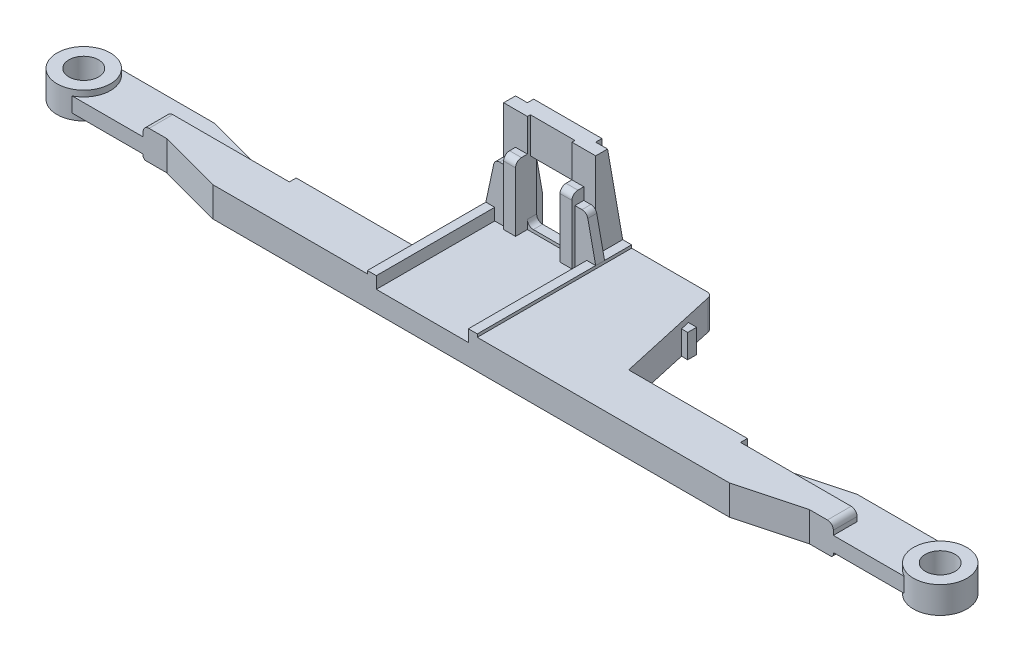
SolidWorks part; units mm, degrees
material "ABS PC"
ref_plane "Piano frontale" through (0, 0, 0) normal (0, 0, 1) x (1, 0, 0)
ref_plane "Piano superiore" through (0, 0, 0) normal (0, 1, 0) x (1, 0, 0)
ref_plane "Piano destro" through (0, 0, 0) normal (1, 0, 0) x (0, 0, -1)
sketch "Schizzo1" plane through (0, 0, 0) normal (0, 1, 0) x (1, 0, 0)
  line L0 (0, 0) -> (-121.1472, 0) construction
  line L1 (43.5, 0) -> (-43.5, 0)
  line L3 (-43.5, 0) -> (-54.1252, 2.847)
  line L4 (-54.1252, 2.847) -> (-72.1252, 2.847)
  line L5 (43.5, 0) -> (54.1252, 2.847)
  line L6 (54.1252, 2.847) -> (72.1252, 2.847)
  line L7 (0, 0) -> (119.0724, 0) construction
  line L8 (-72.1252, 10.847) -> (-54.1252, 10.847)
  line L9 (-54.1252, 10.847) -> (-43.5, 8)
  line L10 (-43.5, 8) -> (43.5, 8)
  line L11 (-43.5, 0) -> (-43.5, 8) construction
  line L12 (54.1252, 10.847) -> (72.1252, 10.847)
  line L13 (-72.1252, 2.847) -> (-72.1252, 6.847) construction
  line L14 (-54.1252, 2.847) -> (-54.1252, 10.847) construction
  line L15 (43.5, 8) -> (54.1252, 10.847)
  line L16 (43.5, 0) -> (43.5, 8) construction
  arc A0 (-72.1252, 10.847) -> (-72.1252, 2.847) centre (-72.1252, 6.847) ccw
  arc A1 (72.1252, 2.847) -> (72.1252, 10.847) centre (72.1252, 6.847) ccw
  circle A2 centre (-72.1252, 6.847) radius 2.5
  circle A3 centre (72.1252, 6.847) radius 2.5
  point P6 (0, 0)
  dimension "D2" = 8
  dimension "D5" = 8
  dimension "D13" = 5
  dimension "D14" = 5
  dimension "D1" = 87
  dimension "D3" = 15
  dimension "D4" = 15
  dimension "D6" = 18
  dimension "D7" = 18
  dimension "D8" = 11
  dimension "D9" = 11
  dimension "D10" = 11
  dimension "D11" = 8
  dimension "D12" = 11
extrude "Estrusione-Estrusione1" add sketch "Schizzo1" along normal mid plane 2.5
sketch "Schizzo2" plane through (0, 0, 0) normal (0, 1, 0) x (1, 0, 0)
  circle A0 centre (-72.1252, 6.847) radius 4.5
  circle A1 centre (-72.1252, 6.847) radius 2.5
  dimension "D1" = 9
  dimension "D2" = 5
extrude "Estrusione-Estrusione2" add sketch "Schizzo2" along normal mid plane 4.5
mirror "Specchia1" about plane through (0, 0, 0) normal (1, 0, 0) of "Estrusione-Estrusione2"
sketch "Schizzo7" plane through (0, 0, 0) normal (0, 1, 0) x (1, 0, 0)
  line L0 (-17.5, 8) -> (-17.5, 26)
  line L1 (43.5, 8) -> (-43.5, 8) construction
  line L2 (-17.5, 26) -> (14.5, 26)
  line L3 (14.5, 26) -> (18.5, 8)
  line L5 (-17.5, 8) -> (-37.5, 8)
  line L6 (-37.5, 8) -> (-37.5, 6.847)
  line L7 (-37.5, 6.847) -> (-58.1252, 6.847)
  line L9 (-54.1252, 2.847) -> (-43.5, 0)
  line L10 (-43.5, 0) -> (43.5, 0)
  line L11 (-43.5, 0) -> (43.5, 0) construction
  line L12 (43.5, 0) -> (54.1252, 2.847)
  line L13 (54.1252, 2.847) -> (58.1252, 2.847)
  line L14 (54.1252, 2.847) -> (70.0636, 2.847) construction
  line L15 (58.1252, 2.847) -> (58.1252, 6.847)
  line L16 (58.1252, 6.847) -> (38.5, 6.847)
  line L17 (38.5, 6.847) -> (38.5, 8)
  line L18 (38.5, 8) -> (18.5, 8)
  line L19 (-54.1252, 2.847) -> (-58.1252, 2.847)
  line L20 (-70.0636, 2.847) -> (-54.1252, 2.847) construction
  line L21 (-58.1252, 2.847) -> (-58.1252, 6.847)
  dimension "D1" = 26
  dimension "D2" = 25
  dimension "D3" = 32
  dimension "D4" = 20
  dimension "D5" = 20
  dimension "D6" = 4
  dimension "D7" = 4
  dimension "D8" = 4
  dimension "D9" = 4
extrude "Estrusione-Estrusione3" add sketch "Schizzo7" along normal blind 3 and the other way blind 2 contours L2 L3 L18 L17 L16 L15 L13 L12 L10 L9 L19 L21 L7 L6 L5 L0
fillet "Raccordo1" radius 1 1 edges at (-58.1252, 3, -4.847)
fillet "Raccordo2" radius 1 1 edges at (58.1252, 3, -4.847)
sketch "Schizzo8" plane through (0, 3, 0) normal (0, 1, 0) x (1, 0, 0)
  line L0 (-17.5, 0) -> (-17.5, 26)
  line L1 (-43.5, 0) -> (43.5, 0) construction
  line L2 (-17.5, 26) -> (14.5, 26) construction
  line L3 (-17.5, 8) -> (-17.5, 26) construction
  line L4 (-17.5, 26) -> (-16, 26)
  line L5 (-16, 26) -> (-16, 0)
  line L6 (-16, 0) -> (-17.5, 0)
  dimension "D1" = 1.5
extrude "Estrusione-Estrusione4" add sketch "Schizzo8" along normal blind 0.5
sketch "Schizzo9" plane through (0, 3, 0) normal (0, 1, 0) x (1, 0, 0)
  line L0 (1, 26) -> (1, 0)
  line L1 (-16, 26) -> (14.5, 26) construction
  line L2 (-16, 0) -> (43.5, 0) construction
  line L3 (1, 0) -> (-0.5, 0)
  line L4 (-0.5, 0) -> (-0.5, 26)
  line L5 (-0.5, 26) -> (1, 26)
  line L6 (-16, 0) -> (-16, 26) construction
  dimension "D1" = 1.5
  dimension "D2" = 15.5
extrude "Estrusione-Estrusione5" add sketch "Schizzo9" along normal blind 0.5
sketch "Schizzo10" plane through (0, 3, 0) normal (0, 1, 0) x (1, 0, 0)
  line L1 (-16, 26) -> (-0.5, 26)
  line L2 (-16, 26) -> (-16, 0)
  line L3 (-16, 0) -> (-0.5, 0)
  line L4 (-0.5, 26) -> (-0.5, 0)
extrude "Taglio-Estrusione1" cut sketch "Schizzo10" against normal blind 1.5
sketch "Schizzo11" plane through (-16, 0, 0) normal (1, 0, 0) x (0, 0, -1)
  line L0 (26, 1.5) -> (26, 3.5)
  line L1 (23.4433, 18) -> (21.4433, 18)
  line L2 (21.4433, 18) -> (21.4433, 1.5)
  line L3 (26, 3.5) -> (23.4433, 18)
  line L5 (21.4433, 1.5) -> (26, 1.5)
  line L6 (26, 3.5) -> (26, 1.5) construction
  line L7 (26, 1.5) -> (0, 1.5) construction
  line L8 (26, -2) -> (8, -2) construction
  dimension "D1" = 10
  dimension "D2" = 2
  dimension "D3" = 20
extrude "Estrusione-Estrusione6" add sketch "Schizzo11" along normal blind 2 contours L5 L0 L3 L1 L2
sketch "Schizzo12" plane through (-0.5, 0, 0) normal (-1, 0, 0) x (0, 0, 1)
  line L0 (-26, 1.5) -> (-26, 3.5)
  line L1 (-26, 3.5) -> (-26, 1.5) construction
  line L2 (-26, -2) -> (-26, 3) construction
  line L3 (-26, 3.5) -> (-23.4433, 18)
  line L5 (-21.4433, 1.5) -> (-26, 1.5)
  line L6 (0, 1.5) -> (-26, 1.5) construction
  line L7 (-23.4433, 18) -> (-21.4433, 18)
  line L8 (-21.4433, 18) -> (-21.4433, 1.5)
  dimension "D1" = 10
  dimension "D2" = 20
  dimension "D3" = 2
extrude "Estrusione-Estrusione7" add sketch "Schizzo12" along normal blind 2
sketch "Schizzo15" plane through (-2.5, 0, 0) normal (-1, 0, 0) x (0, 0, 1)
  line L0 (-23.4433, 18) -> (-26, 3.5) construction
  line L1 (-21.4433, 1.5) -> (-23.0012, 1.5)
  line L2 (-21.4433, 1.5) -> (-21.4433, 18)
  line L3 (-21.4433, 18) -> (-23.4433, 18)
  line L4 (-23.0012, 1.5) -> (-23.0012, 12)
  line L5 (-23.4433, 18) -> (-24.5012, 18)
  line L7 (-23.0012, 12) -> (-24.5012, 12)
  line L8 (-24.5012, 18) -> (-24.5012, 12)
  dimension "D1" = 6
  dimension "D2" = 1.5
extrude "Estrusione-Estrusione8" add sketch "Schizzo15" along normal up to surface (11.5 mm away) up to face at (-14, 8.5, -23.666)
sketch "Schizzo16" plane through (0, 0, -21.4433) normal (0, 0, 1) x (1, 0, 0)
  line L1 (-16, 18) -> (-16, 3.5) construction
  line L3 (-0.5, 3.5) -> (-0.5, 18) construction
  line L4 (-14, 12) -> (-2.5, 12)
  line L5 (-14, 18) -> (-14, 12)
  line L6 (-2.5, 18) -> (-14, 18)
  line L7 (-2.5, 12) -> (-2.5, 18)
  line L8 (-12, 12) -> (-4.5, 12)
  line L9 (-12, 18) -> (-12, 12)
  line L10 (-4.5, 18) -> (-12, 18)
  line L11 (-4.5, 12) -> (-4.5, 18)
  dimension "D2" = 4
  dimension "D3" = 4
  dimension "D1" = 0
extrude "Taglio-Estrusione2" cut sketch "Schizzo16" against normal blind 0.5
sketch "Schizzo17" plane through (0, 0, -21.4433) normal (0, 0, 1) x (1, 0, 0)
  line L0 (-12, 12) -> (-4.5, 12) construction
  line L2 (-12, 12) -> (-4.5, 12)
  line L3 (-12, 12) -> (-12, 3)
  line L4 (-11, 2) -> (-5.5, 2)
  line L5 (-4.5, 12) -> (-4.5, 3)
  line L9 (-16, 1.5) -> (-0.5, 1.5) construction
  line L15 (-14, 12) -> (-2.5, 12)
  line L16 (-14, 18) -> (-14, 12)
  line L17 (-2.5, 18) -> (-14, 18)
  line L18 (-2.5, 12) -> (-2.5, 18)
  line L19 (-14, 12) -> (-2.5, 12) construction
  line L20 (-14, 18) -> (-14, 12) construction
  line L21 (-2.5, 18) -> (-14, 18) construction
  line L22 (-2.5, 12) -> (-2.5, 18) construction
  arc A0 (-5.5, 2) -> (-4.5, 3) centre (-5.5, 3) ccw
  arc A1 (-12, 3) -> (-11, 2) centre (-11, 3) ccw
  point P0 (-8.25, 12)
  dimension "D1" = 1
  dimension "D2" = 2
  dimension "D3" = 0.5
  dimension "D4" = 0
extrude "Taglio-Estrusione3" cut sketch "Schizzo17" against normal through all
sketch "Schizzo18" plane through (0, 0, -21.4433) normal (0, 0, 1) x (1, 0, 0)
  line L3 (-12, 18) -> (-12, 3) construction
  line L4 (-12, 12.5) -> (-14, 12.5)
  line L5 (-12, 12.5) -> (-12, 1.5)
  line L6 (-12, 1.5) -> (-14, 1.5)
  line L7 (-14, 12.5) -> (-14, 1.5)
  line L9 (-16, 1.5) -> (-0.5, 1.5) construction
  line L10 (-12, 12) -> (-4.5, 12) construction
  dimension "D1" = 0.5
  dimension "D2" = 2
extrude "Estrusione-Estrusione13" add sketch "Schizzo18" along normal blind 2
fillet "Raccordo3" radius 1 1 edges at (-13, 12.5, -19.4433)
ref_plane "Piano1" through (-8.25, 0, 0) normal (1, 0, 0) x (0, 0, -1)
mirror "Specchia3" about plane through (-8.25, 0, 0) normal (1, 0, 0) of "Raccordo3", "Estrusione-Estrusione13"
sketch3d "Schizzo3D2"
  line L0 (-14, 12.5, -21.4433) -> (-14, 1.5, -21.4433) construction
  line L1 (-14, 10.5, -21.4433) -> (-16, 10.5, -21.4433)
  line L4 (-16, 1.5, -21.4433) -> (-14, 1.5, -21.4433)
  line L5 (-14, 1.5, -21.4433) -> (-14, 10.5, -21.4433)
  line L6 (-17.5, 3.5, -26) -> (-17.5, 3.5, 0) construction
  line L7 (-16, 1.5, -21.4433) -> (-16, 3.5, -21.4433)
  line L8 (-16, 3.5, -21.4433) -> (-17.5, 3.5, -21.4433)
  line L9 (-12, 12.5, -21.4433) -> (-14, 12.5, -21.4433) construction
  line L10 (-16, 10.5, -21.4433) -> (-17.5, 3.5, -21.4433)
  line L12 (-16, 3.5, -26) -> (-17.5, 3.5, -26) construction
  dimension "D1" = 2
  dimension "D2" = 2
extrude "Estrusione-Estrusione14" add sketch "Schizzo3D2" along direction (0, 0, -1) on the side of the normal blind 1.5 contours L8 L10 L1 L5 L4 L7
fillet "Raccordo4" radius 1 1 edges
mirror "Specchia4" about plane through (-8.25, 0, 0) normal (1, 0, 0) of "Estrusione-Estrusione14", "Raccordo4"
fillet "Raccordo5" radius 0.5 1 edges at (58.1252, -2, -4.847)
fillet "Raccordo6" radius 0.5 1 edges at (-58.1252, -2, -4.847)
shell "Svuota1" thickness 1 removed face at (0, -2, -7.6735)
sketch "Schizzo19" plane through (0, 1.5, 0) normal (0, 1, 0) x (1, 0, 0)
  line L4 (-14, 26) -> (-14, 23.0012)
  line L5 (-14, 23.0012) -> (-2.5, 23.0012)
  line L6 (-2.5, 23.0012) -> (-2.5, 26)
  line L7 (-2.5, 26) -> (-14, 26)
  line L8 (-14, 26) -> (-14, 23.0012)
  line L9 (-14, 23.0012) -> (-2.5, 23.0012)
  line L10 (-2.5, 23.0012) -> (-2.5, 26)
  line L11 (-2.5, 26) -> (-14, 26)
  dimension "D1" = 0
extrude "Taglio-Estrusione4" cut sketch "Schizzo19" against normal through all
ref_plane "Piano2" through (0, 0, -20.9433) normal (0, 0, 1) x (-1, 0, 0)
sketch "Schizzo20" plane through (0, 0, -20.9433) normal (0, 0, 1) x (-1, 0, 0)
  line L0 (16.5, -0.5) -> (16.5, 2)
  line L1 (16.5, -0.5) -> (13, -0.5) construction
  line L2 (16.5, 2) -> (8.5, 2)
  line L3 (8.5, 2) -> (8.5, 5)
  line L4 (8.5, 5) -> (2, 5)
  line L5 (2, 5) -> (2, 9)
  line L6 (2, 9) -> (-5, 9)
  line L7 (-5, 9) -> (-5, 5)
  line L8 (-5, 5) -> (-11, 5)
  line L9 (-11, 5) -> (-11, 2)
  line L10 (-11, 2) -> (-17, 2)
  line L11 (-17, 2) -> (-17, -2)
  line L12 (-17, -2) -> (-0.5, -2)
  line L13 (-0.5, -2) -> (-0.5, -0.5)
  line L14 (-0.5, -0.5) -> (16.5, -0.5)
  line L15 (2.5, 2) -> (-14.5, 2) construction
  line L18 (16.5, 2) -> (16.5, -0.5) construction
  line L22 (-0.5, -2) -> (0, -2) construction
  line L25 (-11, 2) -> (-16.0298, 2) construction
  dimension "D1" = 3
  dimension "D2" = 4
  dimension "D3" = 7
  dimension "D4" = 6.5
  dimension "D5" = 6
  dimension "D6" = 8
  dimension "D7" = 6
extrude "Estrusione-Estrusione17" add sketch "Schizzo20" along normal blind 1.5 contours L10 L11 L12 L13 L14 L0 L2 L3 L4 L5 L6 L7 L8 L9
sketch "Schizzo24" plane through (0, 0, -19.4433) normal (0, 0, 1) x (1, 0, 0)
  line L0 (0.5, 0.5) -> (-16.5, 0.5) construction
  line L1 (-8.5, -2) -> (-6.5, -2)
  line L2 (-8.5, -2) -> (-8.5, 0.5)
  line L3 (-8.5, 0.5) -> (-6.5, 0.5)
  line L4 (-6.5, -2) -> (-6.5, 0.5)
  line L5 (-16.5, -2) -> (-8.5, -2) construction
  dimension "D1" = 2
extrude "Estrusione-Estrusione19" add sketch "Schizzo24" along normal up to surface (18.4433 mm away)
sketch "Schizzo25" plane through (0, 0, -19.4433) normal (0, 0, 1) x (1, 0, 0)
  line L0 (0.5, 2) -> (14.9327, 2) construction
  line L1 (11, -2) -> (9, -2)
  line L2 (11, -2) -> (11, 2)
  line L3 (11, 2) -> (9, 2)
  line L4 (9, -2) -> (9, 2)
  dimension "D1" = 2
extrude "Estrusione-Estrusione20" add sketch "Schizzo25" along normal up to surface (18.4433 mm away) up to face at (-22.9561, 0.1667, -1)
fillet "Raccordo7" radius 1 1 edges at (14.5, 0.5, -26)
